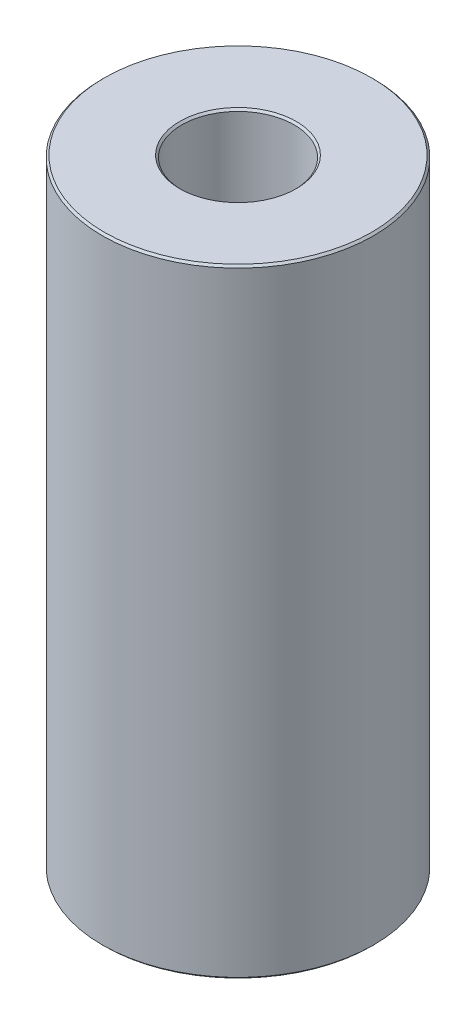
SolidWorks part; units mm, degrees
ref_plane "Front Plane" through (0, 0, 0) normal (0, 0, 1) x (1, 0, 0)
ref_plane "Top Plane" through (0, 0, 0) normal (0, 1, 0) x (1, 0, 0)
ref_plane "Right Plane" through (0, 0, 0) normal (1, 0, 0) x (0, 0, -1)
sketch "Sketch1" plane through (0, 0, 0) normal (0, 1, 0) x (1, 0, 0)
  circle A0 centre (0, 0) radius 47.5
  dimension "SLEEVE_OD" = 95
extrude "Boss-Extrude1" add sketch "Sketch1" along normal blind 216.3867
sketch "Sketch2" plane through (0, 0, 0) normal (0, 1, 0) x (1, 0, 0)
  circle A0 centre (0, 0) radius 19.7051
  dimension "BORE_D" = 39.4101
extrude "Cut-Extrude1" cut sketch "Sketch2" along normal through all
chamfer "Chamfer1" distance 0.7002 angle 45 4 edges at (0, 216.3867, 19.7051) (0, 0, 19.7051) (0, 0, 47.5) (0, 216.3867, 47.5)
